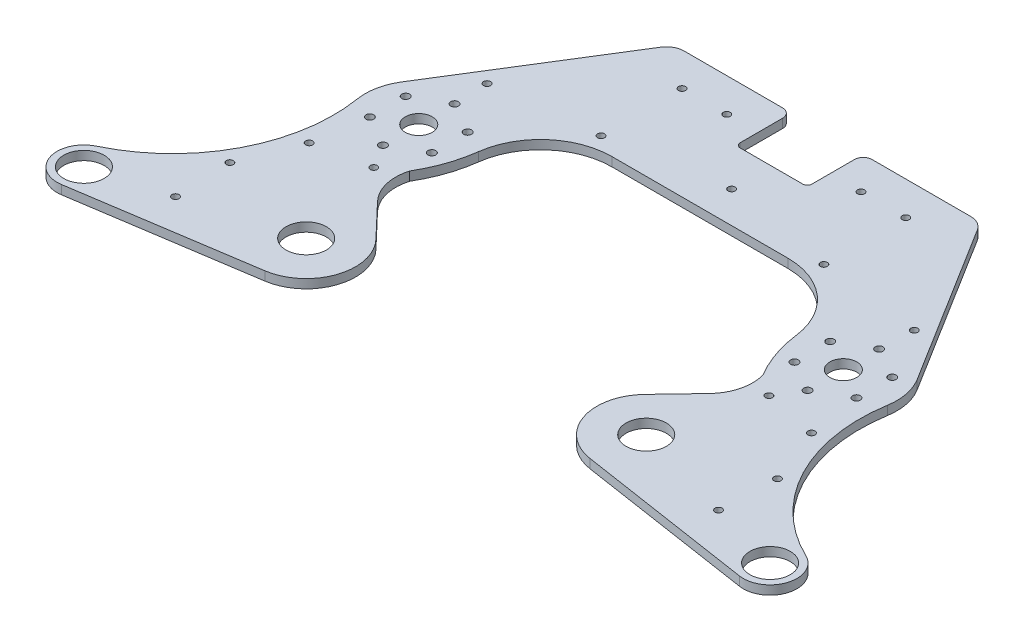
SolidWorks part; units mm, degrees
other "Marca1"
sketch "Croquis4" plane through (-508, 6.35, -221.5657) normal (0, 1, 0) x (1, 0, 0)
sketch "Croquis5" plane through (-262.5313, 6.35, -249.2375) normal (0, 1, 0) x (1, 0, 0)
sketch "Croquis6" plane through (-161.9393, 4.5, -121.1622) normal (0, 1, 0) x (1, 0, 0)
sketch "Croquis7" plane through (-262.5313, 6.35, -249.2375) normal (0, 1, 0) x (1, 0, 0)
sketch "Croquis9" plane through (-161.9393, 10.85, -121.1622) normal (0, 1, 0) x (1, 0, 0)
sketch "Croquis10" plane through (-262.5313, 6.35, -249.2375) normal (0, 1, 0) x (1, 0, 0)
sketch "Croquis12" plane through (-264.3199, 10.85, -20.8386) normal (0, 1, 0) x (1, 0, 0)
sketch "Croquis15" plane through (-262.5313, 6.35, -249.2375) normal (0, 1, 0) x (1, 0, 0)
sketch "Croquis16" plane through (-262.5313, 6.35, -249.2375) normal (0, 1, 0) x (1, 0, 0)
sketch "Croquis17" plane through (-262.5313, 6.35, -249.2375) normal (0, 1, 0) x (1, 0, 0)
sketch "Croquis18" plane through (-262.5313, 6.35, -249.2375) normal (0, 1, 0) x (1, 0, 0)
sketch "Croquis19" [suppressed] plane through (-264.3199, 10.85, -20.8386) normal (0, 1, 0) x (1, 0, 0)
sketch "Croquis20" [suppressed] plane through (-161.9393, 10.85, -121.1622) normal (0, 1, 0) x (1, 0, 0)
sketch "Croquis21" plane through (-264.3199, 10.85, -20.8386) normal (0, 1, 0) x (1, 0, 0)
material "Acrílico (Impacto medio-alto)"
ref_plane "Alzado" through (0, 0, 0) normal (0, 0, 1) x (1, 0, 0)
ref_plane "Planta" through (0, 0, 0) normal (0, 1, 0) x (1, 0, 0)
ref_plane "Vista lateral" through (0, 0, 0) normal (1, 0, 0) x (0, 0, -1)
sketch "Dibujo" plane through (0, 0, 0) normal (0, 1, 0) x (1, 0, 0)
  line L0 (0, 0) -> (0, 158.75) construction
  line L1 (0, 158.75) -> (-508, 158.75) construction
  line L2 (-125.8733, 18.3704) -> (-248.7046, -16.5546) construction
  line L3 (-238.258, -53.2954) -> (-115.4267, -18.3704) construction
  line L4 (-160.1534, 108.938) -> (-149.1603, -2.8048) construction
  line L5 (-141.9901, 113.8973) -> (-94.6704, 12.0732) construction
  circle A0 centre (-120.65, 0) radius 50.8
  circle A1 centre (-243.4813, -34.925) radius 28.575
  arc A2 (-248.7046, -16.5546) -> (-238.258, -53.2954) centre (-243.4813, -34.925) ccw construction
  arc A3 (-115.4267, -18.3704) -> (-125.8733, 18.3704) centre (-120.65, 0) ccw construction
  circle A4 centre (-150.65, 109.8729) radius 30
  arc A5 (-141.9901, 113.8973) -> (-160.1534, 108.938) centre (-150.65, 109.8729) ccw construction
  arc A6 (-149.1603, -2.8048) -> (-94.6704, 12.0732) centre (-120.65, 0) ccw construction
  dimension "D1" = 101.6
  dimension "D5" = 57.15
  dimension "D6" = 38.1972
  dimension "D9" = 60
  dimension "D10" = 19.0986
  dimension "D11" = 57.2958
  dimension "D2" = 241.3
  dimension "D3" = 508
  dimension "D4" = 107.95
  dimension "D8" = 34.925
  dimension "D13" = 241.3
sketch "Croquis2" plane through (0, 0, 0) normal (0, 1, 0) x (1, 0, 0)
  line L0 (-240.6004, -53.7559) -> (-115.3574, -34.5954)
  line L1 (-182.9284, 129.976) -> (-112.3802, 243.2514)
  line L2 (-101.6, 249.2375) -> (101.6, 249.2375)
  line L3 (0, 287.155) -> (0, -59.1328) construction
  line L4 (182.9284, 129.976) -> (112.3802, 243.2514)
  line L5 (240.6004, -53.7559) -> (115.3574, -34.5954)
  line L6 (-95.3203, 24.1508) -> (-117.9194, 47.853)
  line L7 (-141.9901, 113.8973) -> (-94.6704, 12.0732) construction
  line L8 (0, 158.75) -> (-508, 158.75) construction
  line L9 (-62.4132, 158.75) -> (62.4132, 158.75)
  line L10 (95.3203, 24.1508) -> (117.9194, 47.853)
  line L12 (0, 158.75) -> (0, -117.475) construction
  line L13 (-117.475, -117.475) -> (117.475, -117.475) construction
  line L14 (-117.475, -117.475) -> (-117.475, 117.475) construction
  line L15 (-117.475, 117.475) -> (117.475, 117.475) construction
  line L16 (117.475, -117.475) -> (117.475, 117.475) construction
  line L17 (-117.475, -117.475) -> (117.475, 117.475) construction
  line L18 (-117.475, 117.475) -> (117.475, -117.475) construction
  line L20 (-25.4381, 249.2375) -> (25.4381, 249.2375)
  line L21 (-25.4381, 249.2375) -> (-25.4381, 209.55)
  line L22 (-25.4381, 209.55) -> (25.4381, 209.55)
  line L23 (25.4381, 249.2375) -> (25.4381, 209.55)
  line L24 (-25.4381, 249.2375) -> (25.4381, 209.55) construction
  line L25 (-25.4381, 209.55) -> (25.4381, 249.2375) construction
  circle A0 centre (-243.4813, -34.925) radius 14.3256
  circle A1 centre (-120.65, 0) radius 14.3256
  circle A3 centre (-243.4813, -34.925) radius 19.05
  circle A4 centre (-120.65, 0) radius 34.9979
  arc A6 (-149.1603, -2.8048) -> (-94.6704, 12.0732) centre (-120.65, 0) ccw construction
  arc A7 (-188.1821, 103.7596) -> (-251.6976, -17.7379) centre (-300.9954, 85.3844) cw
  arc A8 (-112.3802, 243.2514) -> (-101.6, 249.2375) centre (-101.6, 236.5375) cw
  arc A10 (-117.9194, 47.853) -> (-125.3591, 78.1101) centre (-95.246, 69.4712) cw
  arc A11 (112.3802, 243.2514) -> (101.6, 249.2375) centre (101.6, 236.5375) ccw
  arc A12 (188.1821, 103.7596) -> (251.6976, -17.7379) centre (300.9954, 85.3844) ccw
  arc A13 (-112.7986, 114.4272) -> (-62.4132, 158.75) centre (-62.4132, 107.95) cw
  arc A14 (182.9284, 129.976) -> (188.1821, 103.7596) centre (150.65, 109.8729) cw
  circle A15 centre (120.65, 0) radius 34.9979
  circle A16 centre (243.4813, -34.925) radius 19.05
  circle A17 centre (150.65, 109.8729) radius 9.5631
  circle A18 centre (120.65, 0) radius 14.3256
  circle A19 centre (243.4813, -34.925) radius 14.3256
  circle A20 centre (-150.65, 109.8729) radius 25.4 construction
  circle A21 centre (-150.65, 135.2729) radius 2.75
  circle A22 centre (-128.653, 122.5729) radius 2.75
  circle A23 centre (-128.653, 97.1729) radius 2.75
  circle A24 centre (-150.65, 84.4729) radius 2.75
  circle A25 centre (-172.647, 97.1729) radius 2.75
  circle A26 centre (-172.647, 122.5729) radius 2.75
  circle A27 centre (150.65, 109.8729) radius 25.4 construction
  circle A28 centre (172.647, 122.5729) radius 2.75
  circle A29 centre (172.647, 97.1729) radius 2.75
  circle A30 centre (150.65, 84.4729) radius 2.75
  circle A31 centre (128.653, 97.1729) radius 2.75
  circle A32 centre (128.653, 122.5729) radius 2.75
  circle A33 centre (150.65, 135.2729) radius 2.75
  arc A35 (-182.9284, 129.976) -> (-188.1821, 103.7596) centre (-150.65, 109.8729) ccw
  arc A36 (112.7986, 114.4272) -> (62.4132, 158.75) centre (62.4132, 107.95) ccw
  arc A37 (125.3591, 78.1101) -> (112.7986, 114.4272) centre (206.3577, 126.4546) cw
  circle A39 centre (-150.65, 109.8729) radius 9.5631
  circle A40 centre (-120.65, 0) radius 50.8 construction
  circle A41 centre (-150.65, 109.8729) radius 36.35 construction
  arc A42 (117.9194, 47.853) -> (125.3591, 78.1101) centre (95.246, 69.4712) ccw
  circle A43 centre (-150.65, 109.8729) radius 30 construction
  arc A44 (-125.3591, 78.1101) -> (-112.7986, 114.4272) centre (-206.3577, 126.4546) ccw
  point P53 (0, 249.2375)
  point P71 (-150.65, 109.8729)
  point P88 (-117.2099, 95.6223)
  point P89 (150.65, 109.8729)
  point P93 (0, 158.75)
  point P97 (0, 0)
  point P104 (0, 229.3938)
  dimension "D1" = 28.6512
  dimension "D2" = 6.35
  dimension "D3" = 6.35
  dimension "D4" = 38.1
  dimension "D5" = 114.3
  dimension "D6" = 31.3278
  dimension "D7" = 32.7493
  dimension "D9" = 12.7
  dimension "D11" = 50.8
  dimension "D12" = 5.5
  dimension "D10" = 50.8
  dimension "D14" = 234.95
  dimension "D15" = 94.329
  dimension "D16" = 6.2059
  dimension "D17" = 34.4369
  dimension "D21" = 19.1262
  dimension "D8" = 203.2
  dimension "D18" = 50.8762
  dimension "D19" = 39.6875
  dimension "D20" = 50.8
  dimension "D13" = 6
extrude "Saliente-Extruir1" add sketch "Croquis2" along normal blind 6.35 contours A15 L5 A16 A12 A14 L4 A11 L2 A8 L1 A35 A7 A3 L0 A4 A32 A30 A28 A26 A25 A24 A23 A22 A21 A39 A17 A29 A31 A33 | A15 A18 | A16 A19 | A4 A1 | A3 A0 | L23 L2 L21 L22 | A39 | A25 | A26 | A22 | A23 | A24 | A21 | A17 | A33 | A32 | A28 | A31 | A30 | A29 region at (-224.5706, 0, 51.1627) region at (-261.1719, 0, 40.3755) region at (-152.8373, 0, -10.9784) region at (0, 0, -229.3938) region at (133.2892, 0, -31.5721) region at (259.1411, 0, 25.054) region at (150.65, 0, -109.8729) region at (-150.65, 0, -135.2729) region at (-128.653, 0, -122.5729) region at (-128.653, 0, -97.1729) region at (-150.65, 0, -84.4729) region at (-172.647, 0, -97.1729) region at (-172.647, 0, -122.5729) region at (172.647, 0, -122.5729) region at (172.647, 0, -97.1729) region at (150.65, 0, -84.4729) region at (128.653, 0, -97.1729) region at (128.653, 0, -122.5729) region at (150.65, 0, -135.2729) region at (-150.65, 0, -109.8729)
extrude "Cortar-Extruir1" cut sketch "Croquis2<4>" along normal through all contours L23 L2 L21 L22 | A17 | A29 | A30 | A31 | A32 | A33 | A28 | A39 | A26 | A21 | A22 | A23 | A25 | A24 region at (0, 0, -229.3938) region at (150.65, 0, -109.8729) region at (-150.65, 0, -135.2729) region at (-128.653, 0, -122.5729) region at (-128.653, 0, -97.1729) region at (-150.65, 0, -84.4729) region at (-172.647, 0, -97.1729) region at (-172.647, 0, -122.5729) region at (172.647, 0, -122.5729) region at (172.647, 0, -97.1729) region at (150.65, 0, -84.4729) region at (128.653, 0, -97.1729) region at (128.653, 0, -122.5729) region at (150.65, 0, -135.2729) region at (-150.65, 0, -109.8729)
sketch "Croquis2<4>" plane through (0, 0, 0) normal (0, 1, 0) x (1, 0, 0) same geometry as "Croquis2"
sketch "Croquis14" plane through (0, 6.35, 0) normal (0, 1, 0) x (1, 0, 0)
  line L0 (-240.6004, -53.7559) -> (-115.3574, -34.5954) construction
  line L1 (-101.6, 249.2375) -> (-25.4381, 249.2375) construction
  line L2 (-25.4381, 249.2375) -> (-25.4381, 209.55) construction
  line L5 (0, 158.75) -> (-508, 158.75) construction
  line L7 (-182.9284, 129.976) -> (-112.3802, 243.2514) construction
  line L9 (-62.4132, 158.75) -> (62.4132, 158.75) construction
  line L11 (25.4381, 249.2375) -> (25.4381, 209.55) construction
  line L12 (0, 0) -> (0, 209.55) construction
  line L13 (-25.4381, 209.55) -> (25.4381, 209.55) construction
  circle A0 centre (-192.6813, -20.7294) radius 4.7625
  circle A1 centre (-192.6813, -20.7294) radius 2.4892
  circle A2 centre (-243.4813, -34.925) radius 28.575 construction
  circle A5 centre (-194.31, 19.4563) radius 4.7625
  circle A6 centre (-194.31, 19.4563) radius 2.4892
  circle A7 centre (-178.2433, 59.69) radius 4.7625
  circle A8 centre (-178.2433, 59.69) radius 2.4892
  arc A9 (-251.6976, -17.7379) -> (-188.1821, 103.7596) centre (-300.9954, 85.3844) ccw construction
  circle A10 centre (-47.625, 225.425) radius 4.7625
  circle A11 centre (-47.625, 225.425) radius 2.4892
  circle A12 centre (-79.375, 225.425) radius 4.7625
  circle A13 centre (-79.375, 225.425) radius 2.4892
  circle A14 centre (-120.65, 0) radius 50.8 construction
  circle A15 centre (-140.2263, 67.4904) radius 4.7625
  circle A16 centre (-140.2263, 67.4904) radius 2.4892
  circle A17 centre (47.625, 225.425) radius 2.4892
  circle A18 centre (47.625, 225.425) radius 4.7625
  arc A19 (-125.3591, 78.1101) -> (-117.9194, 47.853) centre (-95.246, 69.4712) ccw construction
  circle A20 centre (79.375, 225.425) radius 2.4892
  circle A21 centre (-150.65, 109.8729) radius 30 construction
  circle A22 centre (0, 181.2925) radius 4.7625
  circle A23 centre (0, 181.2925) radius 2.4892
  circle A24 centre (-79.0522, 167.64) radius 4.7625
  circle A25 centre (-79.0522, 167.64) radius 2.4892
  circle A26 centre (-151.5954, 159.2655) radius 4.7625
  circle A27 centre (-151.5954, 159.2655) radius 2.4892
  circle A28 centre (192.6813, -20.7294) radius 2.4892
  circle A29 centre (192.6813, -20.7294) radius 4.7625
  circle A30 centre (194.31, 19.4563) radius 2.4892
  circle A31 centre (194.31, 19.4563) radius 4.7625
  circle A32 centre (178.2433, 59.69) radius 2.4892
  circle A33 centre (178.2433, 59.69) radius 4.7625
  circle A34 centre (140.2263, 67.4904) radius 2.4892
  circle A35 centre (140.2263, 67.4904) radius 4.7625
  circle A36 centre (79.0522, 167.64) radius 2.4892
  circle A37 centre (79.0522, 167.64) radius 4.7625
  circle A38 centre (151.5954, 159.2655) radius 2.4892
  circle A39 centre (151.5954, 159.2655) radius 4.7625
  circle A40 centre (79.375, 225.425) radius 4.7625
  dimension "D1" = 9.525
  dimension "D2" = 4.9784
  dimension "D3" = 25.4
  dimension "D4" = 50.8
  dimension "D5" = 6.35
  dimension "D6" = 6.35
  dimension "D7" = 8.89
  dimension "D8" = 73.66
  dimension "D9" = 8.89
  dimension "D10" = 7.62
  dimension "D11" = 8.89
  dimension "D12" = 63.5
  dimension "D13" = 17.78
  dimension "D14" = 20.6756
  dimension "D15" = 63.5
  dimension "D16" = 6.35
  dimension "D17" = 23.8125
  dimension "D18" = 22.1869
  dimension "D19" = 31.75
extrude "Cortar-Extruir2" cut sketch "Croquis14" against normal through all contours A1 | A6 | A8 | A16 | A27 | A25 | A23 L12 | L12 A23 | A36 | A38 | A34 | A32 | A30 | A28 | A13 | A11 | A17 | A20 region at (-1.0564, 6.35, -181.2925) region at (1.0564, 6.35, -181.2925) region at (-192.6813, 6.35, 20.7294) region at (-194.31, 6.35, -19.4563) region at (-178.2433, 6.35, -59.69) region at (-47.625, 6.35, -225.425) region at (-79.375, 6.35, -225.425) region at (-140.2263, 6.35, -67.4904) region at (47.625, 6.35, -225.425) region at (79.375, 6.35, -225.425) region at (-79.0522, 6.35, -167.64) region at (-151.5954, 6.35, -159.2655) region at (192.6813, 6.35, 20.7294) region at (194.31, 6.35, -19.4563) region at (178.2433, 6.35, -59.69) region at (140.2263, 6.35, -67.4904) region at (79.0522, 6.35, -167.64) region at (151.5954, 6.35, -159.2655)
fillet "Redondeo1" radius 6.35 2 edges at (25.4381, 3.175, -249.2375) (-25.4381, 3.175, -249.2375)
fillet "Redondeo2" radius 3.175 2 edges at (-25.4381, 3.175, -209.55) (25.4381, 3.175, -209.55)
sketch "Croquis8" [suppressed] plane through (0, 6.35, 0) normal (0, 1, 0) x (1, 0, 0)
  line L0 (-141.9901, 113.8973) -> (-94.6704, 12.0732) construction
  line L1 (-160.1534, 108.938) -> (-149.1603, -2.8048) construction
  line L2 (-141.9901, 113.8973) -> (-94.6704, 12.0732) construction
  line L3 (-160.1534, 108.938) -> (-149.1603, -2.8048) construction
  line L4 (-158.1033, 109.1397) -> (-147.1102, -2.6031)
  line L5 (-143.8583, 113.0292) -> (-96.5386, 11.2051)
  line L6 (-161.8851, 108.7676) -> (-150.8919, -2.9752)
  line L7 (-140.4122, 114.6306) -> (-93.0925, 12.8065)
  arc A0 (-141.9901, 113.8973) -> (-160.1534, 108.938) centre (-150.65, 109.8729) ccw construction
  arc A1 (-149.1603, -2.8048) -> (-94.6704, 12.0732) centre (-120.65, 0) ccw construction
  arc A2 (-141.9901, 113.8973) -> (-160.1534, 108.938) centre (-150.65, 109.8729) ccw construction
  arc A3 (-149.1603, -2.8048) -> (-94.6704, 12.0732) centre (-120.65, 0) ccw construction
  arc A4 (-147.1102, -2.6031) -> (-96.5386, 11.2051) centre (-120.65, 0) ccw
  arc A5 (-143.8583, 113.0292) -> (-158.1033, 109.1397) centre (-150.65, 109.8729) ccw
  arc A6 (-150.8919, -2.9752) -> (-93.0925, 12.8065) centre (-120.65, 0) ccw
  arc A7 (-140.4122, 114.6306) -> (-161.8851, 108.7676) centre (-150.65, 109.8729) ccw
  dimension "D1" = 2.06
  dimension "D2" = 3.8
extrude "Saliente-Extruir2" [suppressed] add sketch "Croquis8" along normal mid plane 9 separate body
delete or keep bodies "Sólido-Eliminar/Conservar 1" [suppressed] type delete bodies bodies 106
sketch "Croquis11" [suppressed] plane through (0, 6.35, 0) normal (0, 1, 0) x (1, 0, 0)
  line L0 (-238.258, -53.2954) -> (-115.4267, -18.3704) construction
  line L1 (-125.8733, 18.3704) -> (-248.7046, -16.5546) construction
  line L2 (-238.258, -53.2954) -> (-115.4267, -18.3704) construction
  line L3 (-125.8733, 18.3704) -> (-248.7046, -16.5546) construction
  line L4 (-125.3099, 16.389) -> (-248.1413, -18.536)
  line L5 (-238.8214, -51.314) -> (-115.9901, -16.389)
  line L6 (-126.3492, 20.0441) -> (-249.1805, -14.8809)
  line L7 (-237.7821, -54.9691) -> (-114.9508, -20.0441)
  arc A0 (-115.4267, -18.3704) -> (-125.8733, 18.3704) centre (-120.65, 0) ccw construction
  arc A1 (-248.7046, -16.5546) -> (-238.258, -53.2954) centre (-243.4813, -34.925) ccw construction
  arc A2 (-115.4267, -18.3704) -> (-125.8733, 18.3704) centre (-120.65, 0) ccw construction
  arc A3 (-248.7046, -16.5546) -> (-238.258, -53.2954) centre (-243.4813, -34.925) ccw construction
  arc A4 (-248.1413, -18.536) -> (-238.8214, -51.314) centre (-243.4813, -34.925) ccw
  arc A5 (-115.9901, -16.389) -> (-125.3099, 16.389) centre (-120.65, 0) ccw
  arc A6 (-249.1805, -14.8809) -> (-237.7821, -54.9691) centre (-243.4813, -34.925) ccw
  arc A7 (-114.9508, -20.0441) -> (-126.3492, 20.0441) centre (-120.65, 0) ccw
  dimension "D1" = 2.06
  dimension "D2" = 3.8
extrude "Saliente-Extruir3" [suppressed] add sketch "Croquis11" along normal mid plane 9 separate body
delete or keep bodies "Sólido-Eliminar/Conservar 2" [suppressed] type delete bodies bodies 106
equation "\"D7@Dibujo\" =  ( 70 * 5mm )  + 1"
equation "\"D10@Dibujo\" = 12 * 5mm / pi"
equation "\"D11@Dibujo\" = 36 * 5mm / pi"
equation "\"D12@Dibujo\" =  ( 70 * 5mm )  + 1mm"
